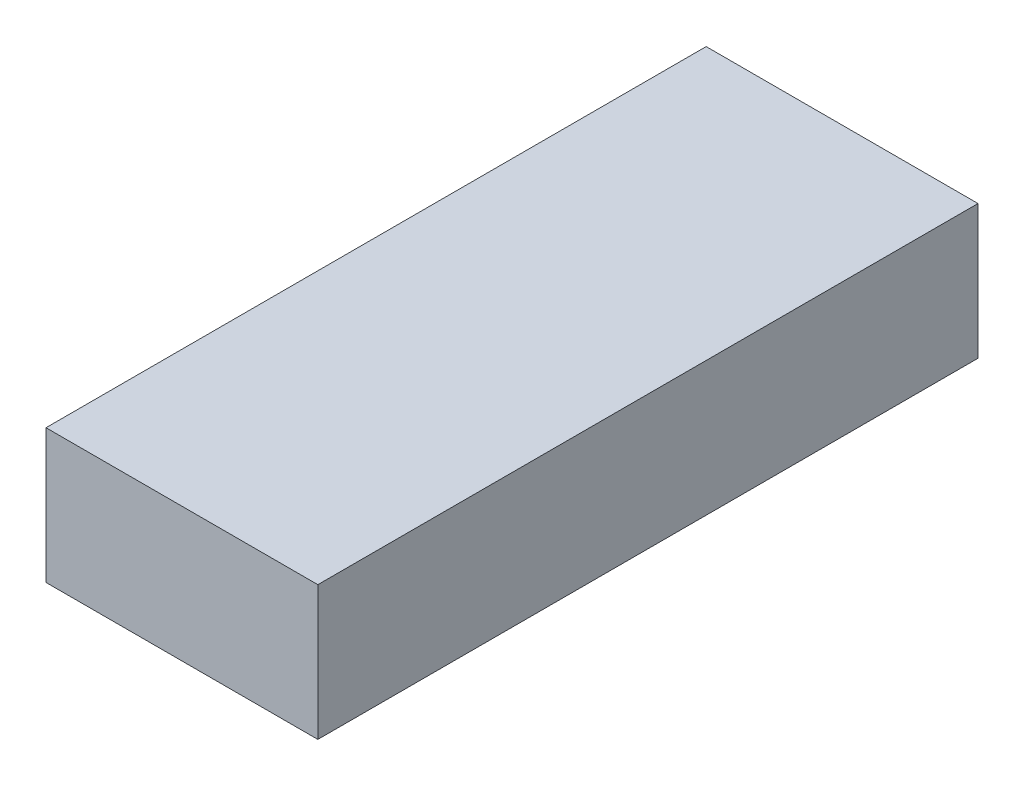
SolidWorks part; units mm, degrees
ref_plane "Front Plane" through (0, 0, 0) normal (0, 0, 1) x (1, 0, 0)
ref_plane "Top Plane" through (0, 0, 0) normal (0, 1, 0) x (1, 0, 0)
ref_plane "Right Plane" through (0, 0, 0) normal (1, 0, 0) x (0, 0, -1)
sketch "Sketch1" plane through (0, 0, 0) normal (0, 1, 0) x (1, 0, 0)
  line L0 (-16.5, 98) -> (-16.5, 1)
  line L1 (-17.5, 99) -> (17.5, 99) construction
  line L2 (-17.5, 99) -> (-17.5, 0) construction
  line L3 (-17.5, 0) -> (17.5, 0) construction
  line L4 (17.5, 99) -> (17.5, 0) construction
  line L5 (-16.5, 1) -> (16.5, 1)
  line L6 (16.5, 98) -> (16.5, 1)
  line L7 (-16.5, 98) -> (16.5, 98)
  line L8 (-17.7, 99.2) -> (-17.7, -0.2)
  line L9 (-17.7, -0.2) -> (17.7, -0.2)
  line L10 (17.7, 99.2) -> (17.7, -0.2)
  line L11 (-17.7, 99.2) -> (17.7, 99.2)
  point P4 (0, 0)
  dimension "D1" = 35
  dimension "D2" = 99
  dimension "D3" = 1
  dimension "D4" = 0.2
extrude "Boss-Extrude1" add sketch "Sketch1" along normal blind 2.4
sketch "Sketch2" plane through (0, 2.4, 0) normal (0, 1, 0) x (1, 0, 0)
  line L0 (-19.7, 101.2) -> (19.7, 101.2)
  line L1 (-17.7, -0.2) -> (17.7, -0.2)
  line L2 (-17.7, -0.2) -> (-17.7, 99.2)
  line L3 (-17.7, 99.2) -> (17.7, 99.2)
  line L4 (17.7, -0.2) -> (17.7, 99.2)
  line L5 (19.7, -2.2) -> (19.7, 101.2)
  line L6 (-19.7, -2.2) -> (19.7, -2.2)
  line L7 (-19.7, -2.2) -> (-19.7, 101.2)
  dimension "D1" = 2
extrude "Boss-Extrude3" add sketch "Sketch2" against normal offset from surface (15.4 mm away) 13 up to face at (0, 0, -49.5) offset beyond the face yes
sketch "Sketch3" plane through (0, 2.4, 0) normal (0, 1, 0) x (1, 0, 0)
  line L1 (-19.7, -2.2) -> (19.7, -2.2)
  line L2 (-19.7, -2.2) -> (-19.7, 101.2)
  line L3 (-19.7, 101.2) -> (19.7, 101.2)
  line L4 (19.7, -2.2) -> (19.7, 101.2)
extrude "Boss-Extrude4" add sketch "Sketch3" along normal blind 2
sketch "Sketch4" plane through (0, 4.4, 0) normal (0, 1, 0) x (1, 0, 0)
  line L0 (21.7, 101.2) -> (21.7, -4.2)
  line L1 (21.7, -4.2) -> (-21.7, -4.2)
  line L2 (-21.7, -4.2) -> (-21.7, 101.2)
  line L3 (-21.7, 101.2) -> (-19.7, 101.2)
  line L4 (19.7, 101.2) -> (21.7, 101.2)
  line L5 (19.7, 101.2) -> (19.7, -2.2)
  line L6 (19.7, -2.2) -> (-19.7, -2.2)
  line L7 (-19.7, -2.2) -> (-19.7, 101.2)
  dimension "D1" = 2
extrude "Boss-Extrude5" add sketch "Sketch4" against normal offset from surface (21.4 mm away) 4 up to face at (0, -13, -49.5) offset beyond the face yes
sketch "Sketch5" plane through (0, -13, 0) normal (0, -1, 0) x (1, 0, 0)
  line L0 (0, -83.2) -> (0, -99.2) construction
  line L1 (-15.2, -23.2) -> (15.2, -23.2) construction
  line L2 (-15.2, -23.2) -> (-15.2, -83.2) construction
  line L3 (-15.2, -83.2) -> (15.2, -83.2) construction
  line L4 (15.2, -23.2) -> (15.2, -83.2) construction
  line L5 (17.7, -99.2) -> (-17.7, -99.2) construction
  line L8 (19.7, -101.2) -> (-19.7, -101.2) construction
  line L10 (-19.7, -101.2) -> (-19.7, 2.2) construction
  circle A0 centre (-15.2, -23.2) radius 5
  circle A1 centre (15.2, -23.2) radius 5
  circle A2 centre (15.2, -83.2) radius 5
  circle A3 centre (-15.2, -83.2) radius 5
  dimension "D1" = 10
  dimension "D2" = 60
  dimension "D3" = 30.4
  dimension "D4" = 18
extrude "Cut-Extrude1" cut sketch "Sketch5" along normal blind 2.4
sketch "Sketch6" plane through (0, -17, 0) normal (0, -1, 0) x (1, 0, 0)
  line L0 (21.7, -101.2) -> (19.7, -101.2) construction
  line L1 (-21.7, 4.2) -> (-17.7, 4.2)
  line L2 (-21.7, 4.2) -> (-21.7, -101.2)
  line L3 (-21.7, -101.2) -> (-17.7, -101.2)
  line L4 (-17.7, 4.2) -> (-17.7, -101.2)
  line L5 (21.7, 4.2) -> (17.7, 4.2)
  line L6 (21.7, 4.2) -> (21.7, -101.2)
  line L7 (21.7, -101.2) -> (17.7, -101.2)
  line L8 (17.7, 4.2) -> (17.7, -101.2)
  line L9 (-17.7, -99.2) -> (-17.7, 0.2) construction
  line L10 (17.7, 0.2) -> (17.7, -99.2) construction
extrude "Boss-Extrude6" add sketch "Sketch6" against normal up to surface (1.6 mm away) up to face at (-19.95, -15.4, -83.2)
chamfer "Chamfer1" distance 0.4 distance2 2 2 edges at (17.7, -15.4, -49.5) (-17.7, -15.4, -49.5) first distance on face at (17.7, -16.2, -49.5) first distance on face at (-17.7, -16.2, -49.5)
